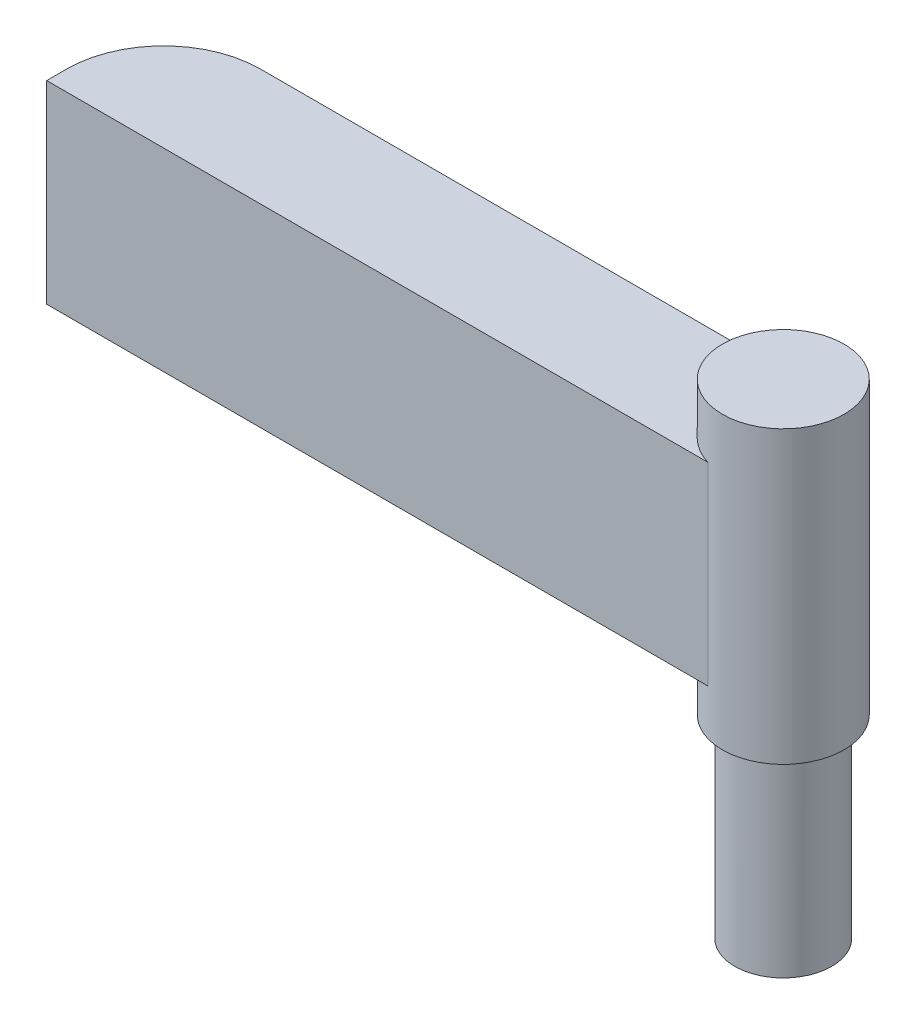
SolidWorks part; units mm, degrees
ref_plane "Front" through (0, 0, 0) normal (0, 0, 1) x (1, 0, 0)
ref_plane "Top" through (0, 0, 0) normal (0, 1, 0) x (1, 0, 0)
ref_plane "Right" through (0, 0, 0) normal (1, 0, 0) x (0, 0, -1)
sketch "Sketch5" plane through (0, 9.3393, 0) normal (0, -1, 0) x (1, 0, 0)
  circle A1 centre (0, 0) radius 0.5
  dimension "D1" = 1
extrude "Boss-Extrude2" add sketch "Sketch5" against normal blind 2
sketch "Sketch8" plane through (0, 11.3393, 0) normal (0, 1, 0) x (1, 0, 0)
  circle A0 centre (0, 0) radius 0.6279
extrude "Boss-Extrude4" add sketch "Sketch8" along normal blind 3
sketch "Sketch11" plane through (0, 0, 0) normal (1, 0, 0) x (0, 0, -1)
  line L1 (-0.6031, 11.8104) -> (0.6031, 11.8104)
  line L2 (-0.6031, 11.8104) -> (-0.6031, 13.8104)
  line L3 (-0.6031, 13.8104) -> (0.6031, 13.8104)
  line L4 (0.6031, 11.8104) -> (0.6031, 13.8104)
  line L5 (-0.6031, 11.8104) -> (0.6031, 13.8104) construction
  line L6 (-0.6031, 13.8104) -> (0.6031, 11.8104) construction
  point P0 (0, 12.8104)
  dimension "D1" = 2
extrude "Boss-Extrude5" add sketch "Sketch11" against normal blind 7
fillet "Fillet1" radius 1 1 edges at (-7, 12.8104, -0.6031)
